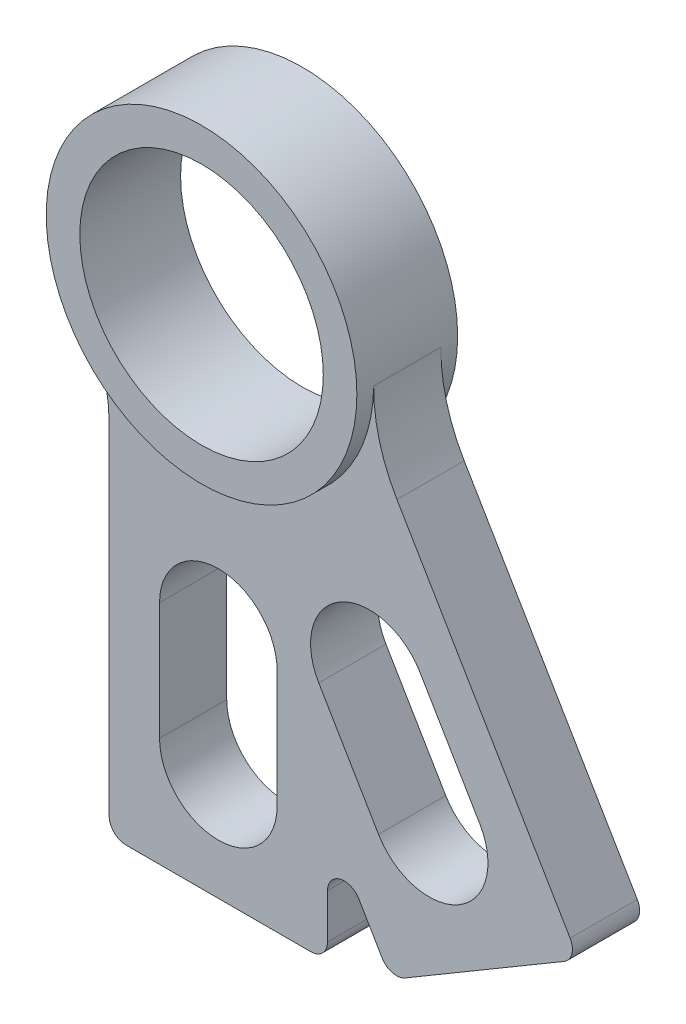
SolidWorks part; units mm, degrees
material "AISI 4130 Steel, annealed at 865C"
ref_plane "X-Y Datum" through (0, 0, 0) normal (0, 0, 1) x (1, 0, 0)
ref_plane "X-Z Datum" through (0, 0, 0) normal (0, 1, 0) x (1, 0, 0)
ref_plane "Y-Z Datum" through (0, 0, 0) normal (1, 0, 0) x (0, 0, -1)
sketch "Sketch1" plane through (0, 0, 0) normal (0, 0, 1) x (1, 0, 0)
  line L0 (0, -39.0706) -> (0, -27.9581) construction
  line L1 (-5.5562, -39.0706) -> (-5.5562, -27.9581)
  line L2 (5.5562, -39.0706) -> (5.5562, -27.9581)
  line L3 (19.9237, -33.7564) -> (14.2754, -24.1865) construction
  line L4 (15.1388, -36.5806) -> (9.4904, -27.0107)
  line L5 (24.7087, -30.9322) -> (19.0603, -21.3623)
  line L6 (-10.3187, -15.7343) -> (-10.3187, -49.3893)
  line L7 (-10.3187, -49.3893) -> (10.3187, -49.3893)
  line L10 (16.2823, -47.8877) -> (34.055, -37.3978)
  line L11 (34.055, -37.3978) -> (16.884, -8.3053)
  line L12 (0, -39.0706) -> (0, 0) construction
  line L13 (0, 0) -> (19.9237, -33.7564) construction
  line L14 (0, -44.6268) -> (0, -49.3893) construction
  line L15 (22.7479, -38.5414) -> (25.1687, -42.6428) construction
  line L16 (21.8845, -26.1472) -> (25.9859, -23.7265) construction
  line L17 (-5.5562, -33.5143) -> (-10.3187, -33.5143) construction
  line L18 (-10.3187, -17.6393) -> (10.3187, -17.6393) construction
  line L19 (10.3187, -17.6393) -> (10.3187, -49.3893) construction
  line L20 (5.5562, -33.5143) -> (10.3187, -33.5143) construction
  line L21 (0, -22.4018) -> (0, -17.6393) construction
  line L22 (16.2823, -47.8877) -> (0.1441, -20.545) construction
  line L23 (0.1441, -20.545) -> (17.9168, -10.0552) construction
  line L24 (12.3146, -31.7956) -> (8.2132, -34.2163) construction
  line L25 (11.4512, -19.4015) -> (9.0304, -15.3001) construction
  line L30 (16.2823, -47.8877) -> (10.3187, -37.7838)
  line L32 (10.3187, -37.7838) -> (10.3187, -49.3893)
  circle A0 centre (0, 0) radius 11.5062
  arc A1 (-5.5562, -39.0706) -> (5.5562, -39.0706) centre (0, -39.0706) ccw
  arc A2 (5.5562, -27.9581) -> (-5.5562, -27.9581) centre (0, -27.9581) ccw
  arc A3 (15.1388, -36.5806) -> (24.7087, -30.9322) centre (19.9237, -33.7564) ccw
  arc A4 (19.0603, -21.3623) -> (9.4904, -27.0107) centre (14.2754, -24.1865) ccw
  arc A5 (14.6808, -0.1135) -> (-12.5852, -7.5598) centre (0, 0) ccw
  arc A6 (16.884, -8.3053) -> (14.6808, -0.1135) centre (30.5553, -0.2362) cw
  arc A7 (-10.3187, -15.7343) -> (-12.5852, -7.5598) centre (-26.1937, -15.7343) ccw
  arc A14 (-12.5852, -7.5598) -> (14.6808, -0.1135) centre (0, 0) ccw
  point P5 (0, -33.5143)
  point P11 (17.0995, -28.9714)
  point P24 (25.1687, -42.6428)
  point P31 (0, -49.3893)
  point P39 (22.7479, -38.5414)
  dimension "D1" = 23.0124
  dimension "D2" = 14.6812
  dimension "D8" = 15.875
  dimension "D9" = 30.55
  dimension "D3" = 20.6375
  dimension "D4" = 4.7625
  dimension "D5" = 31.75
  dimension "D6" = 2.032
  dimension "D7" = 1.905
extrude "Boss-Extrude1" add sketch "Sketch1" along normal mid plane 9.525 contours A14 A7 L6 L7 L32 L30 L10 L11 A6 A4 L5 A3 L4 A2 L2 A1 L1 | A5 A14 A0 region at (8.0962, -29.5305, 0) region at (-3.7584, 13.762, 0)
sketch "Sketch3" plane through (0, 0, 0) normal (0, 0, 1) x (1, 0, 0)
  line L0 (0, -39.0706) -> (0, -27.9581) construction
  line L1 (-5.5562, -39.0706) -> (-5.5562, -27.9581)
  line L2 (5.5562, -39.0706) -> (5.5562, -27.9581)
  line L3 (19.9237, -33.7564) -> (14.2754, -24.1865) construction
  line L4 (15.1388, -36.5806) -> (9.4904, -27.0107)
  line L5 (24.7087, -30.9322) -> (19.0603, -21.3623)
  line L6 (-10.3187, -15.7343) -> (-10.3187, -49.3893)
  line L7 (-10.3187, -49.3893) -> (10.3187, -49.3893)
  line L10 (16.2823, -47.8877) -> (34.055, -37.3978)
  line L11 (34.055, -37.3978) -> (16.884, -8.3053)
  line L12 (0, -39.0706) -> (0, 0) construction
  line L13 (0, 0) -> (19.9237, -33.7564) construction
  line L14 (0, -44.6268) -> (0, -49.3893) construction
  line L15 (22.7479, -38.5414) -> (25.1687, -42.6428) construction
  line L16 (21.8845, -26.1472) -> (25.9859, -23.7265) construction
  line L17 (-5.5562, -33.5143) -> (-10.3187, -33.5143) construction
  line L18 (-10.3187, -17.6393) -> (10.3187, -17.6393) construction
  line L19 (10.3187, -17.6393) -> (10.3187, -49.3893) construction
  line L20 (5.5562, -33.5143) -> (10.3187, -33.5143) construction
  line L21 (0, -22.4018) -> (0, -17.6393) construction
  line L22 (16.2823, -47.8877) -> (0.1441, -20.545) construction
  line L23 (0.1441, -20.545) -> (17.9168, -10.0552) construction
  line L24 (12.3146, -31.7956) -> (8.2132, -34.2163) construction
  line L25 (11.4512, -19.4015) -> (9.0304, -15.3001) construction
  line L30 (16.2823, -47.8877) -> (10.3187, -37.7838)
  line L32 (10.3187, -37.7838) -> (10.3187, -49.3893)
  circle A0 centre (0, 0) radius 11.4954
  arc A1 (-5.5562, -39.0706) -> (5.5562, -39.0706) centre (0, -39.0706) ccw
  arc A2 (5.5562, -27.9581) -> (-5.5562, -27.9581) centre (0, -27.9581) ccw
  arc A3 (15.1388, -36.5806) -> (24.7087, -30.9322) centre (19.9237, -33.7564) ccw
  arc A4 (19.0603, -21.3623) -> (9.4904, -27.0107) centre (14.2754, -24.1865) ccw
  arc A5 (14.6808, -0.1135) -> (-12.5852, -7.5598) centre (0, 0) ccw
  arc A6 (16.884, -8.3053) -> (14.6808, -0.1135) centre (30.5553, -0.2362) cw
  arc A7 (-10.3187, -15.7343) -> (-12.5852, -7.5598) centre (-26.1937, -15.7343) ccw
  arc A14 (-12.5852, -7.5598) -> (14.6808, -0.1135) centre (0, 0) ccw
  point P5 (0, -33.5143)
  point P11 (17.0995, -28.9714)
  point P24 (25.1687, -42.6428)
  point P31 (0, -49.3893)
  point P39 (22.7479, -38.5414)
  dimension "D1" = 22.9908
  dimension "D2" = 14.6812
  dimension "D8" = 15.875
  dimension "D9" = 30.55
  dimension "D3" = 20.6375
  dimension "D4" = 4.7625
  dimension "D5" = 31.75
  dimension "D6" = 2.032
  dimension "D7" = 1.905
extrude "Cut-Extrude1" cut sketch "Sketch3" against normal blind 1.5875 from surface contours A14 A7 L6 L7 L32 L30 L10 L11 A6 A4 L5 A3 L4 A2 L2 A1 L1 region at (8.0962, -29.5305, 0) starting at face at (7.1556, -26.173, 4.7625)
extrude "Cut-Extrude2" cut sketch "Sketch3<11>" along normal blind 1.5875 from surface contours A14 A7 L6 L7 L32 L30 L10 L11 A6 A4 L5 A3 L4 A2 L2 A1 L1 region at (8.0962, -29.5305, 0) starting at face at (7.1556, -26.173, -4.7625)
sketch "Sketch3<11>" plane through (0, 0, 0) normal (0, 0, 1) x (1, 0, 0) same geometry as "Sketch3"
fillet "Fillet1" radius 1.5875 5 edges at (34.055, -37.3978, 0) (16.2823, -47.8877, 0) (10.3187, -37.7838, 0) (10.3187, -49.3893, 0) (-10.3187, -49.3893, 0)
sketch "Sketch4" plane through (0, 0, 4.7625) normal (0, 0, 1) x (1, 0, 0)
  point P0 (0, 0)
sketch "Sketch5" plane through (0, 0, -4.7625) normal (0, 0, -1) x (-1, 0, 0)
  point P0 (0, 0)
